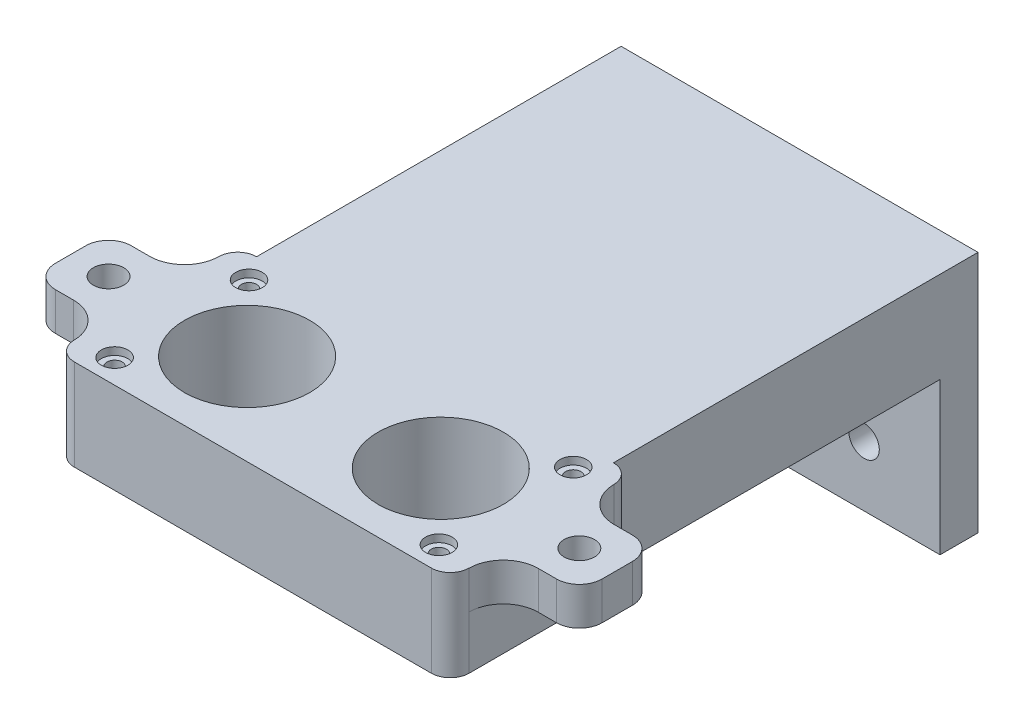
SolidWorks part; units mm, degrees
ref_plane "Front Plane" through (0, 0, 0) normal (0, 0, 1) x (1, 0, 0)
ref_plane "Top Plane" through (0, 0, 0) normal (0, 1, 0) x (1, 0, 0)
ref_plane "Right Plane" through (0, 0, 0) normal (1, 0, 0) x (0, 0, -1)
sketch "Sketch1" plane through (0, 0, 0) normal (0, 1, 0) x (1, 0, 0)
  line L0 (-12.75, 0) -> (12.75, 0) construction
  line L1 (-26, 12) -> (26, 12)
  line L2 (-26, 12) -> (-26, -12)
  line L3 (-26, -12) -> (26, -12)
  line L4 (26, 12) -> (26, -12)
  line L5 (-26, 12) -> (26, -12) construction
  line L6 (-26, -12) -> (26, 12) construction
  circle A0 centre (12.75, 0) radius 8.25
  circle A1 centre (-12.75, 0) radius 8.25
  point P0 (0, 0)
  point P9 (0, 0)
  dimension "D3" = 16.5
  dimension "D1" = 52
  dimension "D2" = 24
  dimension "D4" = 25.5
extrude "Boss-Extrude1" add sketch "Sketch1" along normal blind 12
sketch "Sketch2" plane through (0, 12, 0) normal (0, 1, 0) x (1, 0, 0)
  line L1 (-21.35, 8.85) -> (21.35, 8.85) construction
  line L2 (-21.35, 8.85) -> (-21.35, -8.85) construction
  line L3 (-21.35, -8.85) -> (21.35, -8.85) construction
  line L4 (21.35, 8.85) -> (21.35, -8.85) construction
  line L5 (-21.35, 8.85) -> (21.35, -8.85) construction
  line L6 (-21.35, -8.85) -> (21.35, 8.85) construction
  circle A0 centre (-21.35, 8.85) radius 1
  circle A1 centre (21.35, 8.85) radius 1
  circle A2 centre (21.35, -8.85) radius 1
  circle A3 centre (-21.35, -8.85) radius 1
  point P0 (0, 0)
  dimension "D3" = 2
  dimension "D1" = 17.7
  dimension "D2" = 42.7
extrude "Cut-Extrude1" cut sketch "Sketch2" against normal through all
sketch "Sketch3" plane through (0, 12, 0) normal (0, 1, 0) x (1, 0, 0)
  circle A20 centre (-21.35, 8.85) radius 1.75
  circle A21 centre (21.35, 8.85) radius 1.75
  circle A23 centre (21.35, -8.85) radius 1.75
  circle A24 centre (-21.35, -8.85) radius 1.75
  dimension "D1" = 3.5
extrude "Cut-Extrude2" cut sketch "Sketch3" against normal blind 1
fillet "Fillet1" radius 2.5 4 edges at (26, 6, 12) (-26, 6, 12) (26, 6, -12) (-26, 6, -12)
sketch "Sketch4" plane through (0, 0, 0) normal (0, -1, 0) x (1, 0, 0)
  line L0 (23.5, -12) -> (-23.5, -12) construction
  line L1 (-6, -12) -> (6, -12)
  line L2 (-6, -12) -> (-6, -5)
  line L3 (-6, -5) -> (6, -5)
  line L4 (6, -12) -> (6, -5)
  line L5 (0, -5) -> (0, 0)
  line M14 (-23.5, -12) -> (23.5, -12)
  dimension "D1" = 7
  dimension "D2" = 12
extrude "Cut-Extrude3" cut sketch "Sketch4" against normal blind 5 contours L4 L3 L2 M14 region at (0, 0, -8.5)
fillet "Fillet2" radius 0.5 8 edges at (6, 2.5, -12) (0, 5, -12) (-6, 2.5, -12) (-6, 5, -8.5) (6, 5, -8.5) (6, 2.5, -5) (0, 5, -5) (-6, 2.5, -5)
sketch "Sketch6" plane through (0, 12, 0) normal (0, 1, 0) x (1, 0, 0)
  line L0 (-26, 9.5) -> (-26, -9.5) construction
  line L1 (-26, 5) -> (-36, 5)
  line L2 (-26, 5) -> (-26, -5)
  line L3 (-26, -5) -> (-36, -5)
  line L4 (-36, 5) -> (-36, -5)
  line L5 (0, 0) -> (-36, 0) construction
  line L6 (0, 0) -> (0, 20.5349) construction
  line L7 (36, 5) -> (36, -5)
  line L8 (26, -5) -> (36, -5)
  line L9 (26, 5) -> (26, -5)
  line L10 (26, 5) -> (36, 5)
  circle A0 centre (-31, 0) radius 2
  circle A1 centre (31, 0) radius 2
  dimension "D1" = 4
  dimension "D4" = 5
  dimension "D2" = 10
  dimension "D3" = 10
extrude "Boss-Extrude2" add sketch "Sketch6" against normal blind 5
fillet "Fillet3" radius 4.6 4 edges at (26, 9.5, 5) (-26, 9.5, -5) (-26, 9.5, 5) (26, 9.5, -5)
fillet "Fillet4" radius 3 4 edges at (36, 9.5, -5) (36, 9.5, 5) (-36, 9.5, 5) (-36, 9.5, -5)
sketch "Sketch9" plane through (0, 0, -12) normal (0, 0, -1) x (-1, 0, 0)
  line L1 (-23.5, 12) -> (23.5, 12)
  line L2 (-23.5, 12) -> (-23.5, 0)
  line L3 (-23.5, 0) -> (23.5, 0)
  line L4 (23.5, 12) -> (23.5, 0)
extrude "Boss-Extrude3" add sketch "Sketch9" along normal blind 48
sketch "Sketch11" plane through (0, 0, 0) normal (0, -1, 0) x (1, 0, 0)
  line L0 (23.5, -60) -> (23.5, -12) construction
  line L1 (-23.5, -60) -> (23.5, -60)
  line L2 (-23.5, -60) -> (-23.5, -55)
  line L3 (-23.5, -55) -> (23.5, -55)
  line L4 (23.5, -60) -> (23.5, -55)
  dimension "D1" = 5
extrude "Boss-Extrude5" add sketch "Sketch11" along normal blind 20
sketch "Sketch13" plane through (0, 0, -60) normal (0, 0, -1) x (-1, 0, 0)
  line L0 (23.5, -20) -> (-23.5, -20) construction
  line L1 (-23.5, 12) -> (-23.5, -20) construction
  line L2 (23.5, -20) -> (23.5, 12) construction
  circle A0 centre (0, -12) radius 2
  circle A1 centre (-13.5, -12) radius 2
  circle A2 centre (13.5, -12) radius 2
  dimension "D7" = 4
  dimension "D8" = 4
  dimension "D9" = 4
  dimension "D1" = 8
  dimension "D2" = 23.5
  dimension "D3" = 8
  dimension "D4" = 10
  dimension "D5" = 8
  dimension "D6" = 10
extrude "Cut-Extrude5" cut sketch "Sketch13" against normal up to next
sketch "Sketch16" plane through (0, 0, -60) normal (0, 0, -1) x (-1, 0, 0)
  line L0 (-23.5, 12) -> (-23.5, -20) construction
  line L1 (23.5, -20) -> (-23.5, -20) construction
  circle A0 centre (0, -4) radius 2
  dimension "D3" = 4
  dimension "D1" = 23.5
  dimension "D2" = 16
extrude "Cut-Extrude6" cut sketch "Sketch16" against normal up to next
